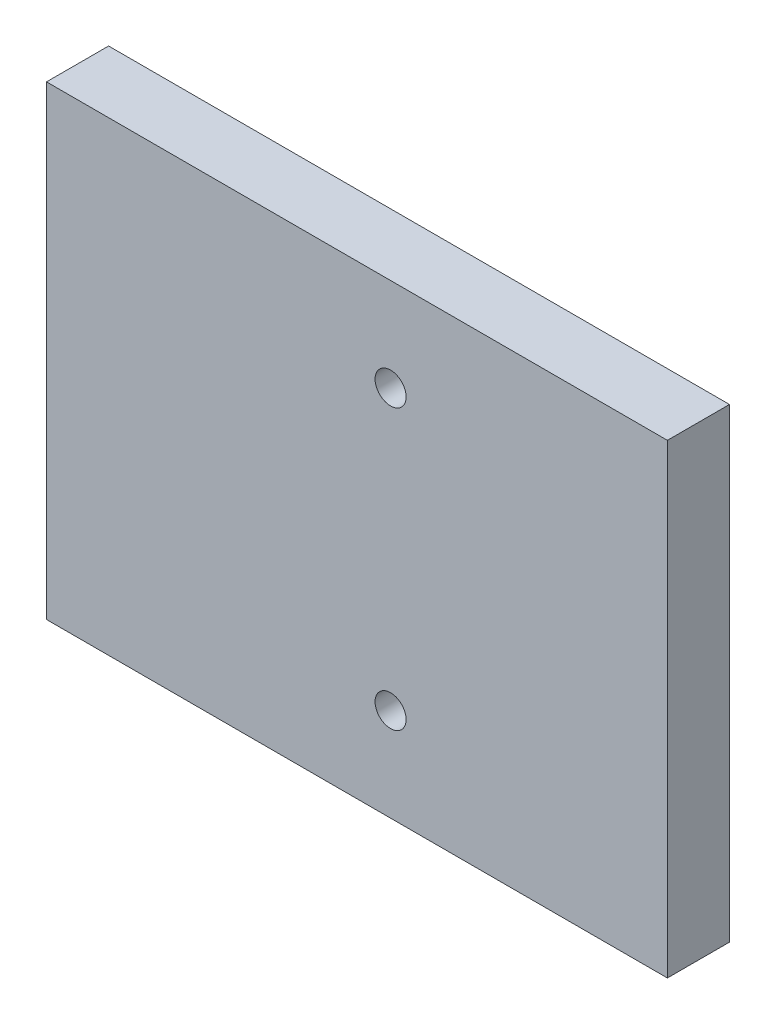
SolidWorks part; units mm, degrees
ref_plane "Front Plane" through (0, 0, 0) normal (0, 0, 1) x (1, 0, 0)
ref_plane "Top Plane" through (0, 0, 0) normal (0, 1, 0) x (1, 0, 0)
ref_plane "Right Plane" through (0, 0, 0) normal (1, 0, 0) x (0, 0, -1)
sketch "Sketch1" plane through (0, 0, 0) normal (0, 0, 1) x (1, 0, 0)
  line L1 (0, 0) -> (60, 0)
  line L2 (0, 0) -> (0, 45)
  line L3 (0, 45) -> (60, 45)
  line L4 (60, 0) -> (60, 45)
  dimension "D1" = 45
  dimension "D2" = 60
extrude "Boss-Extrude1" add sketch "Sketch1" along normal blind 6
extrude "Cut-Extrude1" cut sketch "Sketch2" against normal blind 7.5 and the other way through all
sketch "Sketch2" plane through (67.4346, 22.5, -41.4959) normal (0, 0, 1) x (0, 1, 0)
  circle A0 centre (13.5, 34.1846) radius 1.5
  circle A1 centre (-13.5, 34.1846) radius 1.5
